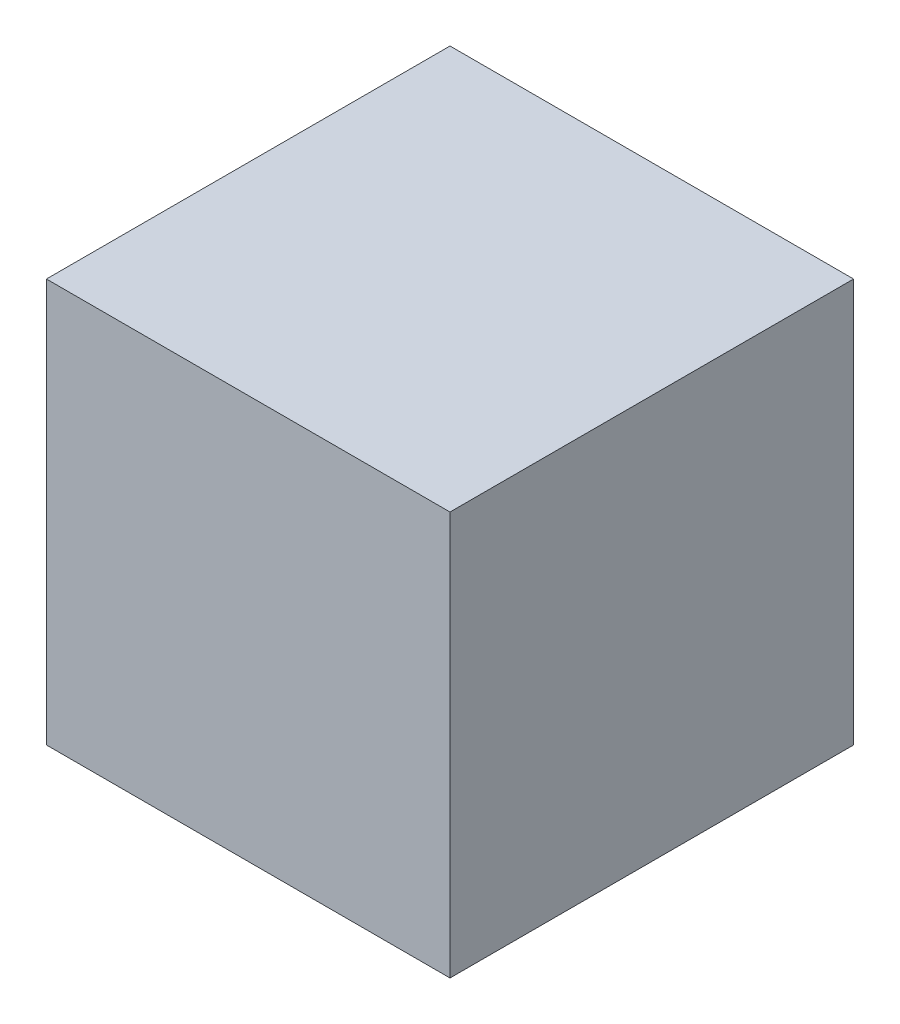
SolidWorks part; units mm, degrees
ref_plane "Ebene vorne" through (0, 0, 0) normal (0, 0, 1) x (1, 0, 0)
ref_plane "Ebene oben" through (0, 0, 0) normal (0, 1, 0) x (1, 0, 0)
ref_plane "Ebene rechts" through (0, 0, 0) normal (1, 0, 0) x (0, 0, -1)
sketch "Sketch1" plane through (0, 0, 0) normal (1, 0, 0) x (0, 0, -1)
  line L0 (-106.9498, 0) -> (127.027, 0) construction
  line L1 (-50, 50) -> (50, 50)
  line L2 (-50, 50) -> (-50, -50)
  line L3 (-50, -50) -> (50, -50)
  line L4 (50, 50) -> (50, -50)
  line L5 (0, 87.8378) -> (0, -79.3436) construction
  dimension "D1" = 100
extrude "Boss-Extrude1" add sketch "Sketch1" along normal blind 100
sketch "Sketch2" plane through (0, 0, 0) normal (-1, 0, 0) x (0, 0, 1)
  circle A0 centre (0, 0) radius 4
  dimension "D1" = 8
extrude "Cut-Extrude1" cut sketch "Sketch2" against normal blind 10
